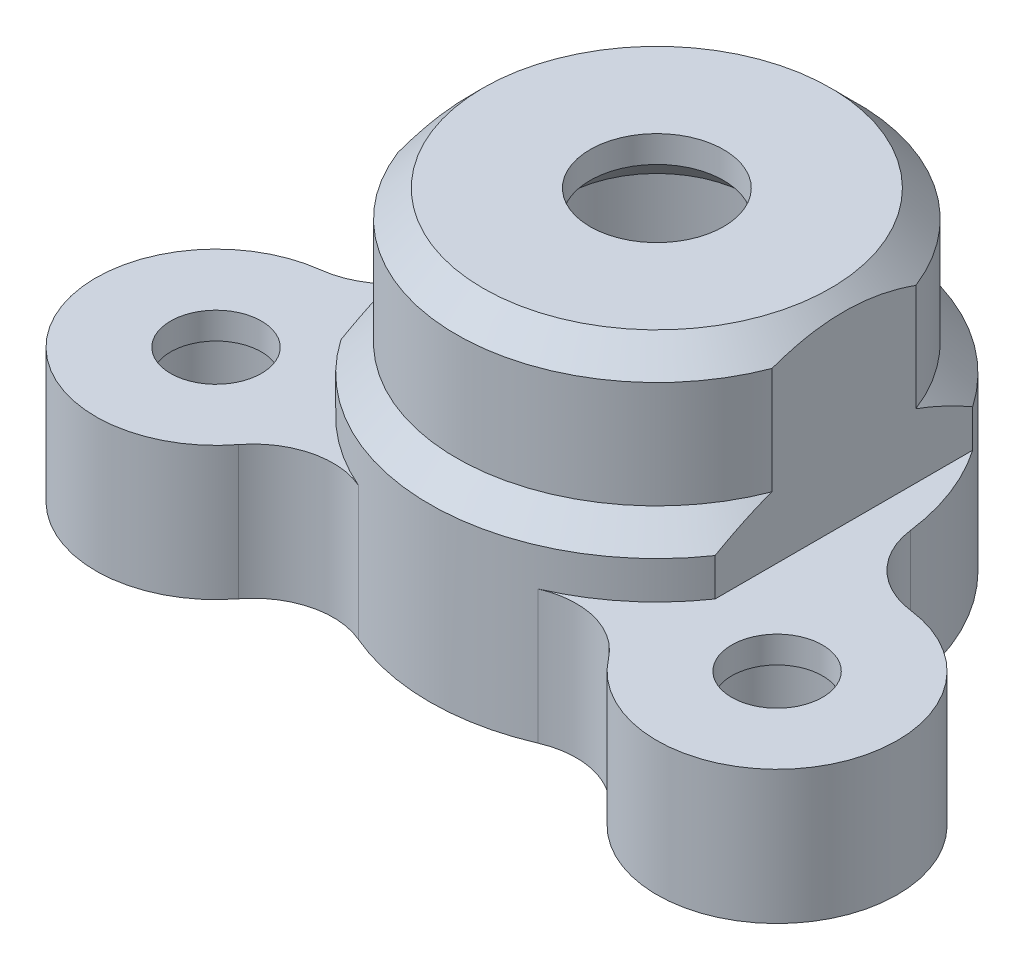
SolidWorks part; units mm, degrees
ref_plane "Plan de face" through (0, 0, 0) normal (0, 0, 1) x (1, 0, 0)
ref_plane "Plan de dessus" through (0, 0, 0) normal (0, 1, 0) x (1, 0, 0)
ref_plane "Plan de droite" through (0, 0, 0) normal (1, 0, 0) x (0, 0, -1)
sketch "Esquisse1" plane through (0, 0, 0) normal (0, 1, 0) x (1, 0, 0)
  line L0 (0, 8.5) -> (0, -8.5) construction
  line L1 (0, 0) -> (-7.3612, 4.25) construction
  line L2 (0, 0) -> (7.3612, 4.25) construction
  line L3 (-10.5, -1.5) -> (-6.3246, -1.5)
  line L4 (10.5, -1.5) -> (6.3246, -1.5)
  circle A0 centre (0, 0) radius 5.5 construction
  circle A2 centre (-10.5, -6) radius 1.7 construction
  arc A3 (-6, -6.0207) -> (6, -6.0207) centre (0, 0) ccw
  circle A4 centre (-10.5, -6) radius 2.5
  arc A5 (-10.5, -1.5) -> (-6, -6.0207) centre (-10.5, -6) ccw
  circle A6 centre (0, 0) radius 6.5
  circle A8 centre (10.5, -6) radius 1.7 construction
  circle A10 centre (10.5, -6) radius 2.5
  arc A11 (10.5, -1.5) -> (6, -6.0207) centre (10.5, -6) cw
  arc A12 (8.3666, -1.5) -> (-8.3666, -1.5) centre (0, 0) ccw construction
  dimension "D1" = 11
  dimension "D4" = 3.4
  dimension "D5" = 2
  dimension "D6" = 3
  dimension "D7" = 5
  dimension "D9" = 1
  dimension "D2" = 10.5
  dimension "D3" = 6
  dimension "D10" = 60
  dimension "D11" = 60
sketch "Esquisse2" plane through (0, 0, 0) normal (0, 0, 1) x (1, 0, 0)
  line L0 (0, 9) -> (0, 0) construction
  line L1 (-2.5, 9) -> (-2.5, 8)
  line L2 (-2.5, 8) -> (-3.5, 7)
  line L3 (-3.5, 7) -> (-5.5, 7)
  line L4 (-5.5, 7) -> (-5.5, 3)
  line L5 (-5.5, 3) -> (-6.5, 2)
  line L7 (-8.5, 0) -> (-8.5, 3)
  line L8 (-8.5, 9) -> (-2.5, 9) construction
  line L9 (-6.5, 2) -> (-6.5, 0)
  line L10 (-8.5, 3) -> (-7.5, 4)
  line L11 (-6.5, 0) -> (-8.5, 0)
  line L12 (-7.5, 4) -> (-7.5, 8)
  line L13 (-8.5, 3) -> (-8.5, 9) construction
  line L14 (-6.5, 9) -> (-2.5, 9)
  line L15 (-7.5, 8) -> (-6.5, 9)
  dimension "D1" = 2.5
  dimension "D2" = 5.5
  dimension "D3" = 2
  dimension "D4" = 1
  dimension "D5" = 1
  dimension "D6" = 4
  dimension "D7" = 1
  dimension "D8" = 8.5
  dimension "D9" = 2
  dimension "D10" = 1
  dimension "D11" = 1
revolve "Révolution1" add sketch "Esquisse2" angle 360 about L0
extrude "Boss.-Extru.1" add sketch "Esquisse1" against normal blind 5 from offset 1.5917 contours A11 A6 A5 A3 A4 A10 | A4 | A10 region at (-8.4123, 0, 1.8132) region at (-10.5, 0, 6) region at (10.5, 0, 6)
extrude "Enlèv. mat.-Extru.3" cut sketch "Esquisse1<7>" along normal blind 4 from surface contours A4 | A10 region at (-10.5, 0, 6) region at (10.5, 0, 6) starting at face at (0, -3.4082, 6.0582)
sketch "Esquisse1<7>" plane through (0, 0, 0) normal (0, 1, 0) x (1, 0, 0) same geometry as "Esquisse1"
hole_wizard "M3 Clearance Hole2" positions "Esquisse9" profile "Esquisse8" hole size "M3" standard "ANSI Metric" end condition up to next
sketch "Esquisse9" plane through (0, -3.4082, 0) normal (0, -1, 0) x (-1, 0, 0)
  point P0 (-10.5, -6)
  point P3 (10.5, -6)
sketch "Esquisse8" plane through (10.5, -3.4082, 6) normal (1, 0, 0) x (0, 0, -1)
  line L0 (0, 0) -> (0, 5)
  line L1 (0, 5) -> (1.7, 5)
  line L2 (1.7, 5) -> (1.7, 0)
  line L5 (1.7, 0) -> (0, 0)
  line L11 (0, -6.35) -> (0, 107.95) construction
  dimension "Thru Hole Dia." = 3.4
  dimension "Thru Hole Depth" = 5
sketch "Esquisse10" plane through (0, -3.4082, 0) normal (0, -1, 0) x (1, 0, 0)
  line L3 (10.5, 1.5) -> (6.3246, 1.5) construction
  line L4 (8.3666, 1.5) -> (6.3246, 1.5) construction
  line L5 (6.3246, 1.5) -> (8.3666, 1.5)
  line L6 (-6.3246, 1.5) -> (-8.3666, 1.5)
  arc A1 (-8.3666, 1.5) -> (8.3666, 1.5) centre (0, 0) ccw
  arc A2 (-6.3246, 1.5) -> (6.3246, 1.5) centre (0, 0) ccw
  line M19 (-10.5, 1.5) -> (-6.3246, 1.5)
  line M21 (6.3246, 1.5) -> (10.5, 1.5)
extrude "Boss.-Extru.3" add sketch "Esquisse10" along normal up to surface from surface contours A2 A1 M19 | A2 A1 | A2 A1 M21 region at (7.3456, -3.4082, 1.3028) up to face at (-10.5, -3.4082, 8.5) starting at face at (0, 0, -3)
sketch "Esquisse11" plane through (0, 9, 0) normal (0, 1, 0) x (1, 0, 0)
  line L0 (-7, 4.8218) -> (-7, -4.8218)
  line L1 (7, 4.8218) -> (7, -4.8218)
  circle A0 centre (0, 0) radius 8.5 construction
  arc A1 (-8.3666, -1.5) -> (-6, -6.0207) centre (0, 0) ccw construction
  arc A2 (-7, -4.8218) -> (-7, 4.8218) centre (0, 0) cw
  arc A3 (7, 4.8218) -> (7, -4.8218) centre (0, 0) cw
  dimension "D1" = 14
extrude "Enlèv. mat.-Extru.5" cut sketch "Esquisse11" against normal up to surface (7.4082 mm away) contours A2 L0 | A3 L1 region at (-7.6048, 9, 0) region at (7.6048, 9, 0) up to face at (-10.5, 1.5918, 7.7)
fillet "Congé5" radius 3 4 edges at (-8.3666, -0.9082, 1.5) (8.3666, -0.9083, 1.5) (6, -0.9082, 6.0207) (-6, -0.9082, 6.0207)
chamfer "Chanfrein5" distance 0.5 angle 45 2 edges at (-10.5, -3.4082, 8.5) (10.5, -3.4082, 8.5)
